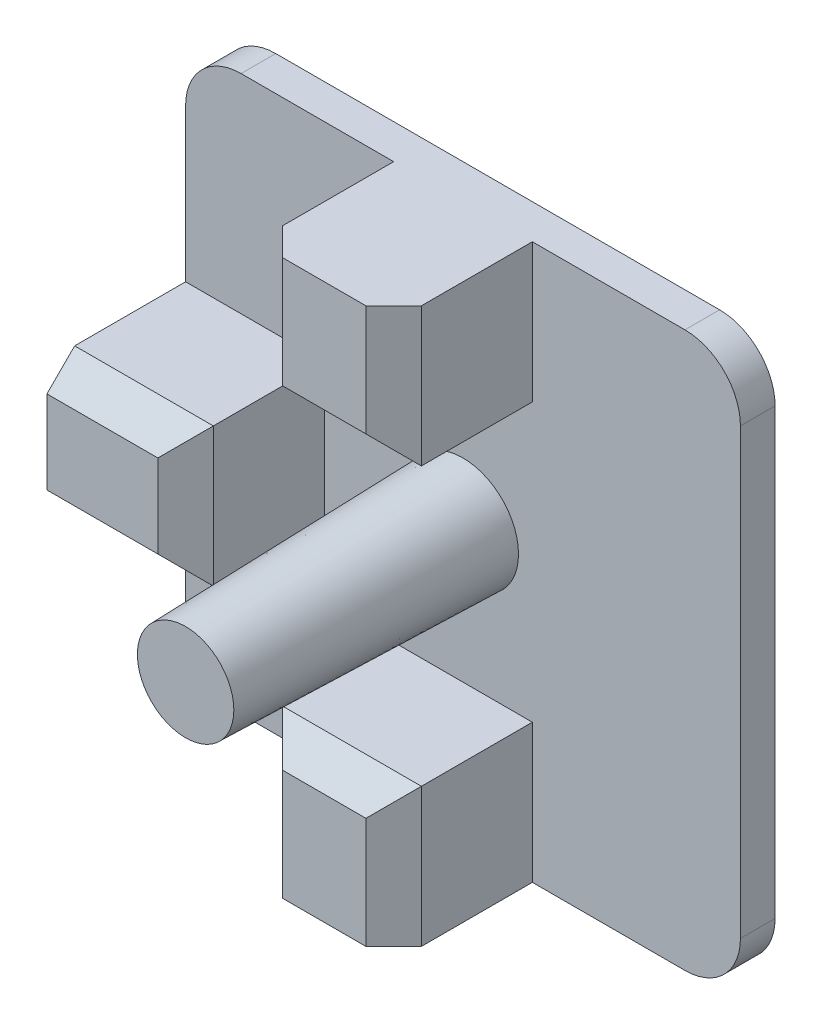
SolidWorks part; units mm, degrees
ref_plane "Front Plane" through (0, 0, 0) normal (0, 0, 1) x (1, 0, 0)
ref_plane "Top Plane" through (0, 0, 0) normal (0, 1, 0) x (1, 0, 0)
ref_plane "Right Plane" through (0, 0, 0) normal (1, 0, 0) x (0, 0, -1)
sketch "Sketch1" plane through (0, 0, 0) normal (0, 0, 1) x (1, 0, 0)
  line L1 (-10.16, 12.7) -> (10.16, 12.7)
  line L2 (-12.7, 10.16) -> (-12.7, -10.16)
  line L3 (-10.16, -12.7) -> (10.16, -12.7)
  line L4 (12.7, 10.16) -> (12.7, -10.16)
  line L5 (-12.7, 12.7) -> (12.7, -12.7) construction
  line L6 (-12.7, -12.7) -> (12.7, 12.7) construction
  arc A0 (10.16, -12.7) -> (12.7, -10.16) centre (10.16, -10.16) ccw
  arc A1 (-12.7, -10.16) -> (-10.16, -12.7) centre (-10.16, -10.16) ccw
  arc A2 (-10.16, 12.7) -> (-12.7, 10.16) centre (-10.16, 10.16) ccw
  arc A3 (10.16, 12.7) -> (12.7, 10.16) centre (10.16, 10.16) cw
  point P0 (0, 0)
  dimension "D3" = 2.54
  dimension "D1" = 25.4
  dimension "D2" = 25.4
extrude "Boss-Extrude1" add sketch "Sketch1" along normal blind 1.5875
sketch "Sketch2" plane through (0, 0, 1.5875) normal (0, 0, 1) x (1, 0, 0)
  line L0 (0, 0) -> (-12.7, 0) construction
  line L1 (-12.7, 10.16) -> (-12.7, -10.16) construction
  line L2 (0, 0) -> (0, -12.7) construction
  line L3 (-10.16, -12.7) -> (10.16, -12.7) construction
  line L4 (-12.7, -3.175) -> (-6.35, -3.175)
  line L5 (-6.35, -3.175) -> (-6.35, 3.175)
  line L6 (-6.35, 3.175) -> (-12.7, 3.175)
  line L7 (3.175, 6.35) -> (3.175, 12.7)
  line L8 (-3.175, 6.35) -> (3.175, 6.35)
  line L9 (-3.175, 12.7) -> (-3.175, 6.35)
  line L10 (6.35, -3.175) -> (12.7, -3.175)
  line L11 (6.35, 3.175) -> (6.35, -3.175)
  line L12 (12.7, 3.175) -> (6.35, 3.175)
  line L13 (-3.175, -6.35) -> (-3.175, -12.7)
  line L14 (3.175, -6.35) -> (-3.175, -6.35)
  line L15 (3.175, -12.7) -> (3.175, -6.35)
  circle A0 centre (0, 0) radius 2.54
  line M9 (10.16, 12.7) -> (-10.16, 12.7)
  line M11 (-12.7, 10.16) -> (-12.7, -10.16)
  line M13 (-10.16, -12.7) -> (10.16, -12.7)
  dimension "D1" = 5.08
  dimension "D2" = 6.35
  dimension "D3" = 3.175
  dimension "D4" = 6.35
  dimension "D5" = 4
extrude "Boss-Extrude3" add sketch "Sketch2" along normal blind 6.35 contours L15 L14 L13 M13 | L5 L6 L4 M11 | L9 L8 L7 M9 region at (-9.525, 0, 1.5875) region at (0, 9.525, 1.5875) region at (0, -9.525, 1.5875)
extrude "Boss-Extrude4" add sketch "Sketch2<4>" along normal blind 12.7 draft 1.5 contours A0 region at (0, 0, 1.5875)
sketch "Sketch2<4>" plane through (0, 0, 1.5875) normal (0, 0, 1) x (1, 0, 0) same geometry as "Sketch2"
chamfer "Chamfer1" distance 1.27 angle 45 9 edges at (3.175, 9.525, 7.9375) (-3.175, 9.525, 7.9375) (0, 6.35, 7.9375) (-9.525, -3.175, 7.9375) (-9.525, 3.175, 7.9375) (-6.35, 0, 7.9375) (-3.175, -9.525, 7.9375) (3.175, -9.525, 7.9375) (0, -6.35, 7.9375)
sketch "Sketch5" plane through (0, 0, 0) normal (0, 0, -1) x (-1, 0, 0)
  circle A0 centre (0, 0) radius 8.4658 construction
  text T0 "UNH" font "Tw Cen MT Condensed Extra Bold" height 3.5
  text T1 "      UNH" font "Tw Cen MT Condensed Extra Bold" height 3.5
  dimension "D1" = 16.9316
extrude "Cut-Extrude1" cut sketch "Sketch5" against normal blind 0.6
